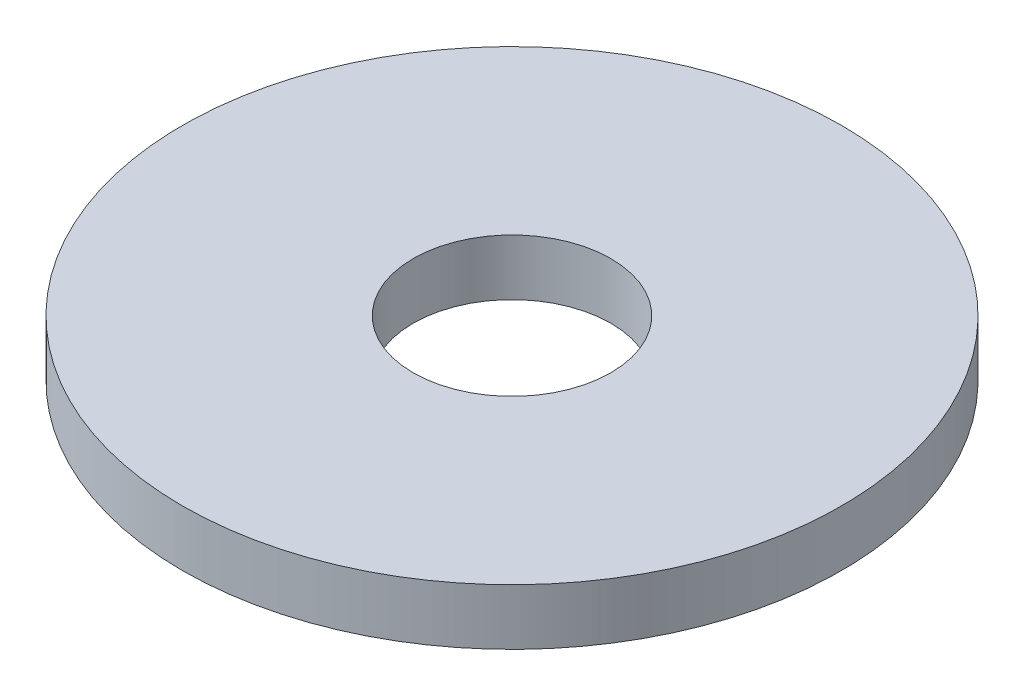
SolidWorks part; units mm, degrees
ref_plane "Front Plane" through (0, 0, 0) normal (0, 0, 1) x (1, 0, 0)
ref_plane "Top Plane" through (0, 0, 0) normal (0, 1, 0) x (1, 0, 0)
ref_plane "Right Plane" through (0, 0, 0) normal (1, 0, 0) x (0, 0, -1)
sketch "Sketch1" plane through (0, 0, 0) normal (0, 1, 0) x (1, 0, 0)
  circle A0 centre (0, 0) radius 100
  dimension "FLANGE_OD" = 200
extrude "Boss-Extrude1" add sketch "Sketch1" along normal blind 17
sketch "Sketch2" plane through (0, 0, 0) normal (0, 1, 0) x (1, 0, 0)
  circle A0 centre (0, 0) radius 30
  dimension "BORE_D" = 60
extrude "Cut-Extrude1" cut sketch "Sketch2" along normal through all
sketch "Sketch3" plane through (0, 17, 0) normal (0, 1, 0) x (1, 0, 0)
  circle A0 centre (0, 0) radius 27.1107 construction
  circle A1 centre (-27.1107, 0) radius 2.8033
  dimension "BOLT_D" = 5.6066
  dimension "BOLT_PCD" = 54.2214
extrude "Cut-Extrude2" cut sketch "Sketch3" against normal blind 14.1856 rebuild error yes
pattern_circular "CirPattern1" count 6 over 360 rebuild error yes
